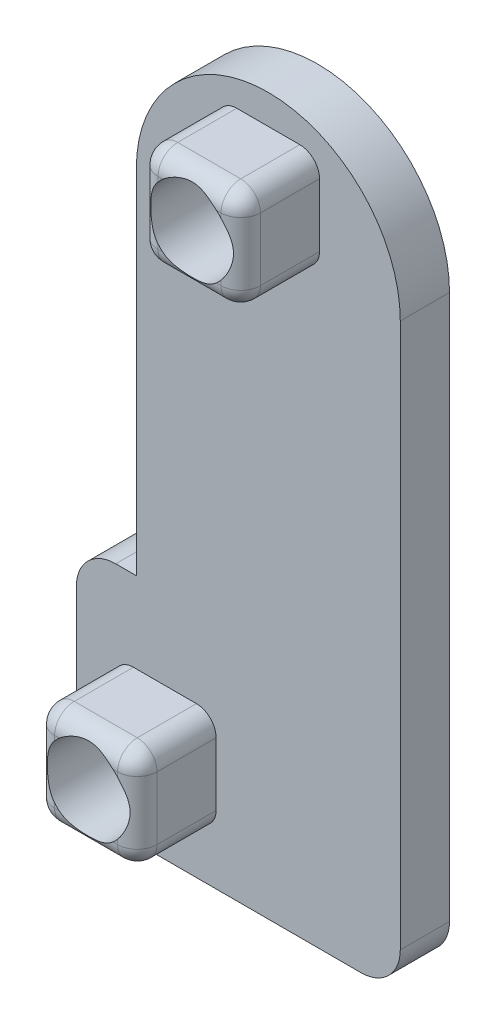
SolidWorks part; units mm, degrees
ref_plane "Front Plane" through (0, 0, 0) normal (1, 0, 0) x (0, 1, 0)
ref_plane "Top Plane" through (0, 0, 0) normal (0, 0, 1) x (0, 1, 0)
ref_plane "Right Plane" through (0, 0, 0) normal (0, 1, 0) x (-1, 0, 0)
sketch "Sketch1" plane through (0, 0, 0) normal (0, 0, 1) x (0, 1, 0)
  line L0 (0, 0) -> (22, 0) construction
  line L1 (-7.6494, 4.1194) -> (-7.6494, 9.7494)
  line L2 (4.1, 6.7) -> (22, 6.7)
  line L3 (0.2, -6.7) -> (22, -6.7)
  line L4 (22, -2.6) -> (27.2, -2.6)
  line L5 (22, -2.6) -> (22, 2.6)
  line L6 (22, 2.6) -> (27.2, 2.6)
  line L7 (27.2, -2.6) -> (27.2, 2.6)
  line L8 (0, 2.65) -> (-5.2, 2.65)
  line L9 (0, 2.65) -> (0, 7.85)
  line L10 (0, 7.85) -> (-5.2, 7.85)
  line L11 (-5.2, 2.65) -> (-5.2, 7.85)
  line L12 (-2.6, 7.85) -> (-2.6, -0.15) construction
  line L13 (4.1, 7.75) -> (4.1, 6.7)
  line L14 (-7.6494, 4.1194) -> (-7.6524, -3.8806)
  line L15 (4.1, 0) -> (4.1, -0.05)
  line L20 (-7.6494, 9.7494) -> (4.1, 9.745)
  line L21 (4.1, 9.745) -> (4.1, 7.75)
  line L22 (-7.6524, -3.8806) -> (-7.6524, -6.7)
  line L23 (-7.6524, -6.7) -> (0.2, -6.7)
  arc A1 (22, -6.7) -> (22, 6.7) centre (22, 0) ccw
  point P5 (10.9, 0)
  point P18 (-2.6, 3.75)
  dimension "D3" = 22
  dimension "D1" = 2.6
  dimension "D2" = 13.4
  dimension "D4" = 5.2
  dimension "D5" = 0
  dimension "D6" = 5.2
  dimension "D7" = 2.65
  dimension "D9" = 8
extrude "Boss-Extrude1" add sketch "Sketch1" along normal blind 2.5 contours L14 L3 A1 L2 L13 L1 L8 L11 L10 L9 L7 L4 L5 L6 | L11 L8 L9 L10 | L4 L7 L6 L5 region at (-0.339, 8.7729, 0) region at (0, 24.6, 0) region at (-5.25, -2.6, 0)
extrude "Boss-Extrude2" add sketch "Sketch1<3>" along normal blind 6.5 contours L11 L10 L9 L8 | L5 L6 L7 L4
sketch "Sketch1<3>" plane through (0, 0, 0) normal (0, 0, 1) x (0, 1, 0) same geometry as "Sketch1"
fillet "Fillet1" radius 2 3 edges at (-9.745, 4.1, 1.25) (-9.7494, -7.6494, 1.25) (6.7, -7.6524, 1.25)
fillet "Fillet2" radius 1 16 edges at (0, 22, 6.5) (-2.6, 24.6, 6.5) (0, 27.2, 6.5) (2.6, 24.6, 6.5) (-5.25, -5.2, 6.5) (-7.85, -2.6, 6.5) (-5.25, 0, 6.5) (-2.65, -2.6, 6.5) (-2.6, 27.2, 4.5) (2.6, 27.2, 4.5) (2.6, 22, 4.5) (-2.6, 22, 4.5) (-7.85, -5.2, 4.5) (-7.85, 0, 4.5) (-2.65, 0, 4.5) (-2.65, -5.2, 4.5)
sketch "Sketch2" plane through (0, 0, 6.5) normal (0, 0, 1) x (1, 0, 0)
  line L0 (0, 26.2) -> (0, 23) construction
  line L1 (1.6, 26.2) -> (-1.6, 26.2) construction
  line L2 (-1.6, 23) -> (1.6, 23) construction
  line L3 (-1.6, 24.6) -> (1.6, 24.6) construction
  line L4 (-1.6, 26.2) -> (-1.6, 23) construction
  line L5 (1.6, 23) -> (1.6, 26.2) construction
  line L6 (-5.25, -1) -> (-5.25, -4.2) construction
  line L7 (-3.65, -1) -> (-6.85, -1) construction
  line L8 (-6.85, -4.2) -> (-3.65, -4.2) construction
  line L9 (-6.85, -2.6) -> (-3.65, -2.6) construction
  line L10 (-6.85, -1) -> (-6.85, -4.2) construction
  line L11 (-3.65, -4.2) -> (-3.65, -1) construction
  circle A0 centre (-5.25, -2.6) radius 2.1
  circle A1 centre (0, 24.6) radius 2.1
  dimension "D1" = 4.2
extrude "Cut-Extrude1" cut sketch "Sketch2" against normal blind 7.5
